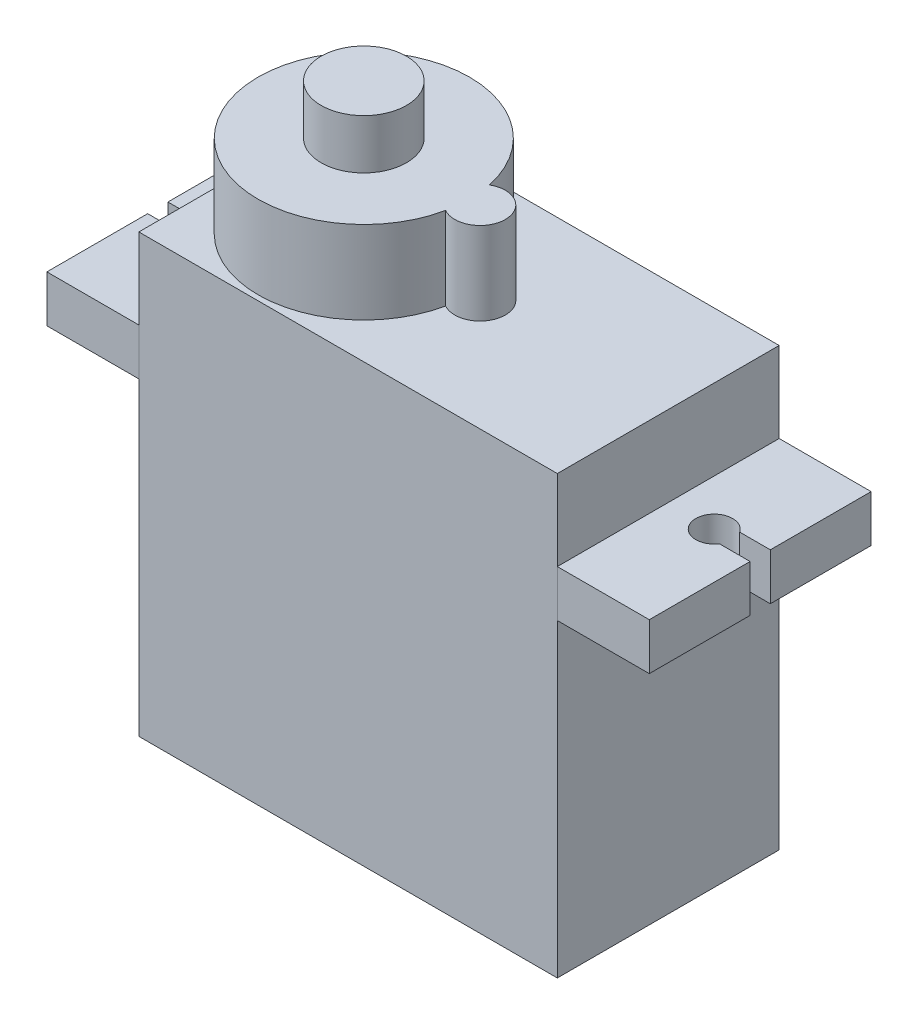
SolidWorks part; units mm, degrees
ref_plane "Front Plane" through (0, 0, 0) normal (0, 0, 1) x (1, 0, 0)
ref_plane "Top Plane" through (0, 0, 0) normal (0, 1, 0) x (1, 0, 0)
ref_plane "Right Plane" through (0, 0, 0) normal (1, 0, 0) x (0, 0, -1)
sketch "Sketch1" plane through (0, 0, 0) normal (0, 1, 0) x (1, 0, 0)
  line L1 (-11.375, -6.03) -> (11.375, -6.03)
  line L2 (-11.375, -6.03) -> (-11.375, 6.03)
  line L3 (-11.375, 6.03) -> (11.375, 6.03)
  line L4 (11.375, -6.03) -> (11.375, 6.03)
  line L5 (-11.375, -6.03) -> (11.375, 6.03) construction
  line L6 (-11.375, 6.03) -> (11.375, -6.03) construction
  point P0 (0, 0)
  dimension "D1" = 22.75
  dimension "D2" = 12.06
extrude "Boss-Extrude1" add sketch "Sketch1" along normal blind 23.75
sketch "Sketch2" plane through (11.375, 0, 0) normal (1, 0, 0) x (0, 0, -1)
  line L0 (-6.03, 23.75) -> (-6.03, 0) construction
  line L1 (-6.03, 19.37) -> (6.03, 19.37)
  line L2 (-6.03, 19.37) -> (-6.03, 16.83)
  line L3 (-6.03, 16.83) -> (6.03, 16.83)
  line L4 (6.03, 19.37) -> (6.03, 16.83)
  line L5 (6.03, 23.75) -> (6.03, 0) construction
  line L6 (-6.03, 23.75) -> (6.03, 23.75) construction
  dimension "D1" = 4.38
  dimension "D2" = 2.54
extrude "Boss-Extrude2" add sketch "Sketch2" along normal blind 5 separate body
sketch "Sketch3" plane through (-11.375, 0, 0) normal (-1, 0, 0) x (0, 0, 1)
  line L4 (6.03, 16.83) -> (6.03, 19.37)
  line L5 (-6.03, 16.83) -> (6.03, 16.83)
  line L6 (-6.03, 19.37) -> (-6.03, 16.83)
  line L7 (6.03, 19.37) -> (-6.03, 19.37)
  line L8 (6.03, 16.83) -> (6.03, 19.37)
  line L9 (-6.03, 16.83) -> (6.03, 16.83)
  line L10 (-6.03, 19.37) -> (-6.03, 16.83)
  line L11 (6.03, 19.37) -> (-6.03, 19.37)
  dimension "D1" = 0
extrude "Boss-Extrude3" add sketch "Sketch3" along normal blind 5 separate body
sketch "Sketch4" plane through (0, 19.37, 0) normal (0, 1, 0) x (1, 0, 0)
  line L0 (-16.375, -6.03) -> (-16.375, 6.03) construction
  line L1 (16.375, 6.03) -> (16.375, -6.03) construction
  line L3 (-16.375, 0.55) -> (-14.7102, 0.55)
  line L4 (-16.375, 0.55) -> (-16.375, -0.55)
  line L5 (-16.375, -0.55) -> (-14.7102, -0.55)
  line L7 (16.375, -0.55) -> (14.7102, -0.55)
  line L8 (16.375, -0.55) -> (16.375, 0.55)
  line L9 (16.375, 0.55) -> (14.7102, 0.55)
  arc A0 (-14.7102, -0.55) -> (-14.7102, 0.55) centre (-13.875, 0) ccw
  arc A1 (14.7102, 0.55) -> (14.7102, -0.55) centre (13.875, 0) ccw
  dimension "D1" = 2
  dimension "D2" = 2
  dimension "D4" = 2.5
  dimension "D3" = 2.5
  dimension "D5" = 1.1
  dimension "D6" = 0.55
  dimension "D7" = 1.1
  dimension "D8" = 0.55
extrude "Cut-Extrude1" cut sketch "Sketch4" against normal up to next (2.54 mm away)
sketch "Sketch5" plane through (0, 19.37, 0) normal (0, 1, 0) x (1, 0, 0)
  line L0 (16.375, 6.03) -> (16.375, -6.03) construction
  line L1 (14.7102, 0.55) -> (16.375, 0.55)
  line L3 (14.7102, -0.55) -> (16.375, -0.55)
  line L4 (16.375, 0.55) -> (16.375, -0.55)
  arc A0 (14.7102, 0.55) -> (14.7102, -0.55) centre (13.875, 0) ccw
  dimension "D1" = 2
  dimension "D2" = 1.1
  dimension "D3" = 0.55
  dimension "D4" = 2.5
extrude "Cut-Extrude2" cut sketch "Sketch5" against normal up to next (2.54 mm away) contours L1 L4 L3 A0
sketch "Sketch6" plane through (0, 23.75, 0) normal (0, 1, 0) x (1, 0, 0)
  line L0 (-11.375, 6.03) -> (-11.375, -6.03) construction
  line L1 (1.125, 1.3944) -> (0.4034, 1.3944)
  line L2 (1.125, -1.3556) -> (0.4129, -1.3556)
  arc A0 (0.4453, 1.2146) -> (0.4526, -1.18) centre (-5.175, 0) ccw
  arc A1 (0.4526, -1.18) -> (0.4453, 1.2146) centre (1.125, 0.0194) ccw
  dimension "D2" = 11.5
  dimension "D3" = 2.75
  dimension "D1" = 6.2
  dimension "D4" = 6.3
extrude "Boss-Extrude4" add sketch "Sketch6" along normal blind 4.5 contours A1 A0 region at (-4.8989, 23.75, -0.0008)
sketch "Sketch7" plane through (0, 28.25, 0) normal (0, 1, 0) x (1, 0, 0)
  circle A0 centre (-5.175, 0) radius 2.32
  dimension "D1" = 4.64
extrude "Boss-Extrude5" add sketch "Sketch7" along normal blind 2.7
sketch "Sketch8" plane through (-11.375, 0, 0) normal (-1, 0, 0) x (0, 0, 1)
  line L0 (-6.03, 0) -> (6.03, 0) construction
  circle A0 centre (-1.2, 4.5) radius 0.6
  circle A1 centre (0, 4.5) radius 0.6
  circle A2 centre (1.2, 4.5) radius 0.6
  dimension "D1" = 4.5
  dimension "D2" = 1.2
  dimension "D3" = 1.2
  dimension "D4" = 1.2
extrude "Boss-Extrude7" add sketch "Sketch8" along normal blind 2.3 separate body contours A1 | A0 | A2 region at (-11.375, 4.5, -1.2) region at (-11.375, 4.5, 1.2) region at (-11.375, 4.5, 0)
